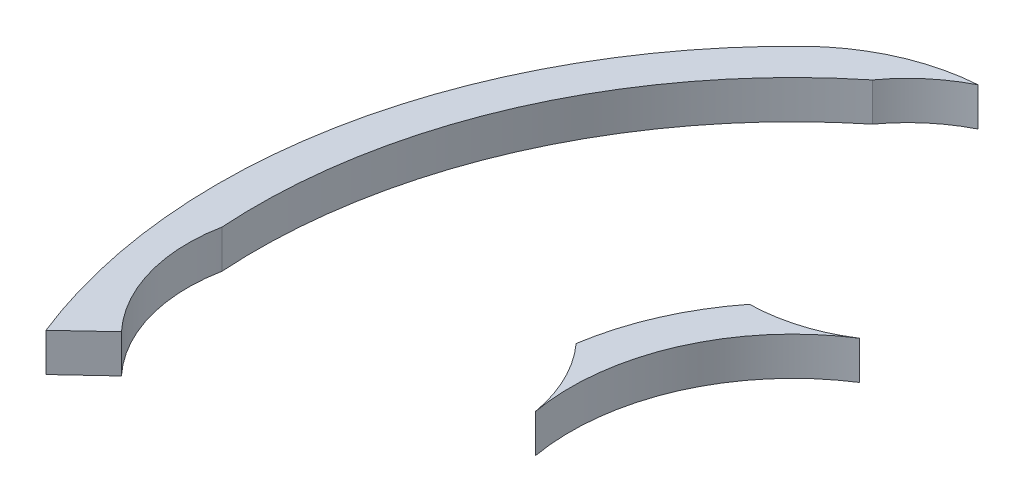
SolidWorks part; units mm, degrees
ref_plane "Plan de face" through (0, 0, 0) normal (0, 0, 1) x (1, 0, 0)
ref_plane "Plan de dessus" through (0, 0, 0) normal (0, 1, 0) x (1, 0, 0)
ref_plane "Plan de droite" through (0, 0, 0) normal (1, 0, 0) x (0, 0, -1)
sketch "Esquisse1" plane through (0, 0, 0) normal (0, 1, 0) x (1, 0, 0)
  line L0 (-85.9864, -39.221) -> (-80.901, -34.4645)
  line L3 (-9.4508, 5.6286) -> (-14.9085, -3.5351) construction
  line L5 (3.3105, -15.9387) -> (9.4508, -5.6286) construction
  line L12 (0, 0) -> (-80, 0) construction
  line L13 (-64.4502, -24.994) -> (-51.2217, 24.3754) construction
  line L14 (-65, 0) -> (-64.4502, -24.994) construction
  arc A0 (-44.8834, -16.4709) -> (3.3105, -15.9387) centre (-21.2415, 25) ccw construction
  arc A1 (-19.868, -3.8238) -> (-14.9085, -3.5351) centre (-17.486, -2) ccw construction
  arc A2 (-19.868, -3.8238) -> (-32.0272, 12.9486) centre (294.4534, 236.8392) cw construction
  arc A3 (-13.5326, 17.4331) -> (-23.8264, -39.4451) centre (-16.3245, -11.4322) ccw
  arc A4 (-43.0332, 9.6068) -> (-49.9076, -6.124) centre (-16.3245, -11.4322) ccw
  arc A5 (-13.0513, 22.4098) -> (-25.1198, -44.2749) centre (-16.3245, -11.4322) ccw construction
  arc A6 (-60.3658, 42.977) -> (-86.1705, -16.0732) centre (-16.3245, -11.4322) ccw
  arc A36 (-51.2217, 24.3754) -> (-64.4502, -24.994) centre (-16.3245, -11.4322) ccw construction
  arc A37 (-68.6703, 42.2792) -> (-85.9864, -39.221) centre (-16.3245, -11.4322) ccw
  arc A41 (9.4508, -5.6286) -> (-9.4508, 5.6286) centre (0, 0) ccw construction
  arc A42 (-16.402, 38.5677) -> (-47.4539, -50.5598) centre (-16.3245, -11.4322) ccw construction
  arc A43 (-52.9274, 49.3171) -> (-32.0272, 12.9486) centre (-43.3981, 30.6037) ccw
  arc A44 (-52.9274, 49.3171) -> (-68.6703, 42.2792) centre (-51.2217, 24.3754) ccw
  arc A45 (-44.8834, -16.4709) -> (-80.901, -34.4645) centre (-65.564, -20.1196) ccw
  point P78 (-56.6847, 2.6915)
  point P85 (-65, 0)
  dimension "D4" = 25
  dimension "D5" = 12
  dimension "D6" = 21
  dimension "D7" = 5
  dimension "D8" = 25
  dimension "D9" = 5
  dimension "D10" = 3
  dimension "D11" = 17.6
  dimension "D18" = 80
  dimension "D20" = 75
  dimension "D26" = 11
  dimension "D13" = 50
  dimension "D14" = 21
  dimension "D12" = 2
  dimension "D22" = 25
  dimension "D23" = 75
  dimension "D24" = 28
  dimension "D25" = 15
  dimension "D30" = 10
  dimension "D32" = 5
extrude "Boss.-Extru.1" add sketch "Esquisse1" along normal blind 5 contours A45 A3 A43 A44 A37 L0 | A45 A3 A43 A4 region at (-88.7429, 0, -3.9543) region at (-44.3251, 0, -0.8039)
